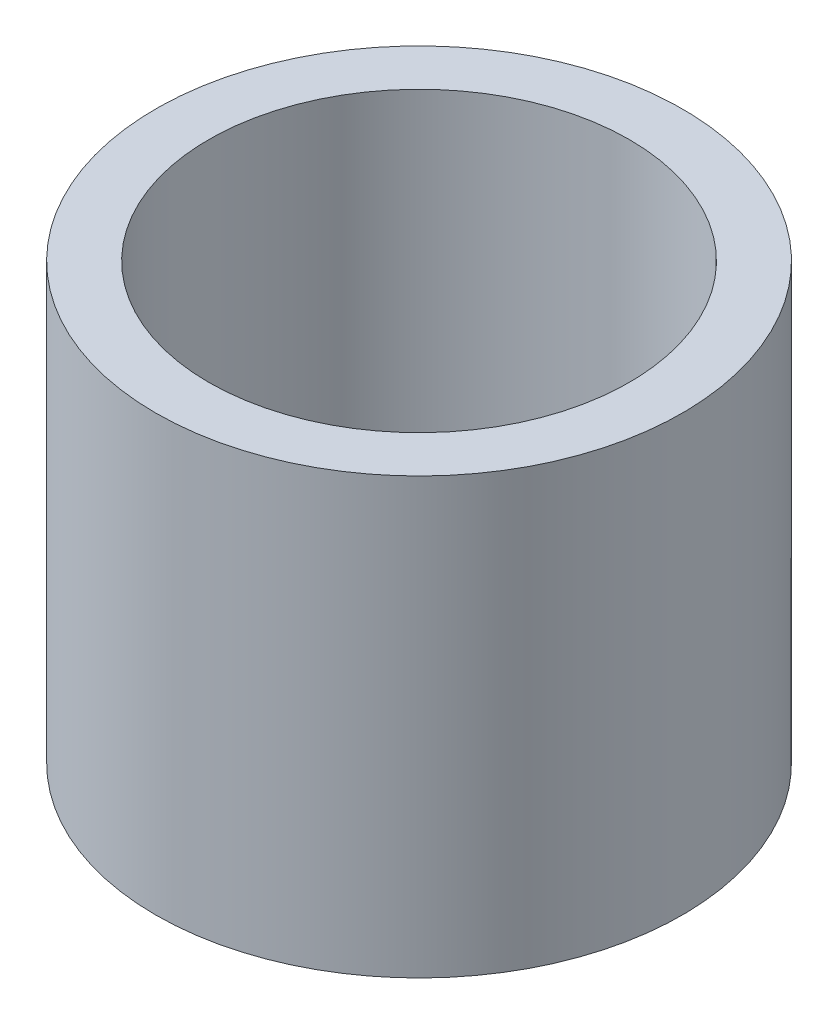
SolidWorks part; units mm, degrees
ref_plane "Front Plane" through (0, 0, 0) normal (0, 0, 1) x (1, 0, 0)
ref_plane "Top Plane" through (0, 0, 0) normal (0, 1, 0) x (1, 0, 0)
ref_plane "Right Plane" through (0, 0, 0) normal (1, 0, 0) x (0, 0, -1)
sketch "Sketch1" plane through (0, 0, 0) normal (0, 1, 0) x (1, 0, 0)
  circle A0 centre (0, 0) radius 22.5
  dimension "SLEEVE_OD" = 45
extrude "Boss-Extrude1" add sketch "Sketch1" along normal blind 37.14
sketch "Sketch2" plane through (0, 0, 0) normal (0, 1, 0) x (1, 0, 0)
  circle A0 centre (0, 0) radius 17.9674
  dimension "BORE_D" = 35.9349
extrude "Cut-Extrude1" cut sketch "Sketch2" along normal through all
chamfer "Chamfer1" distance 3.8498 angle 66.727 rebuild error yes
